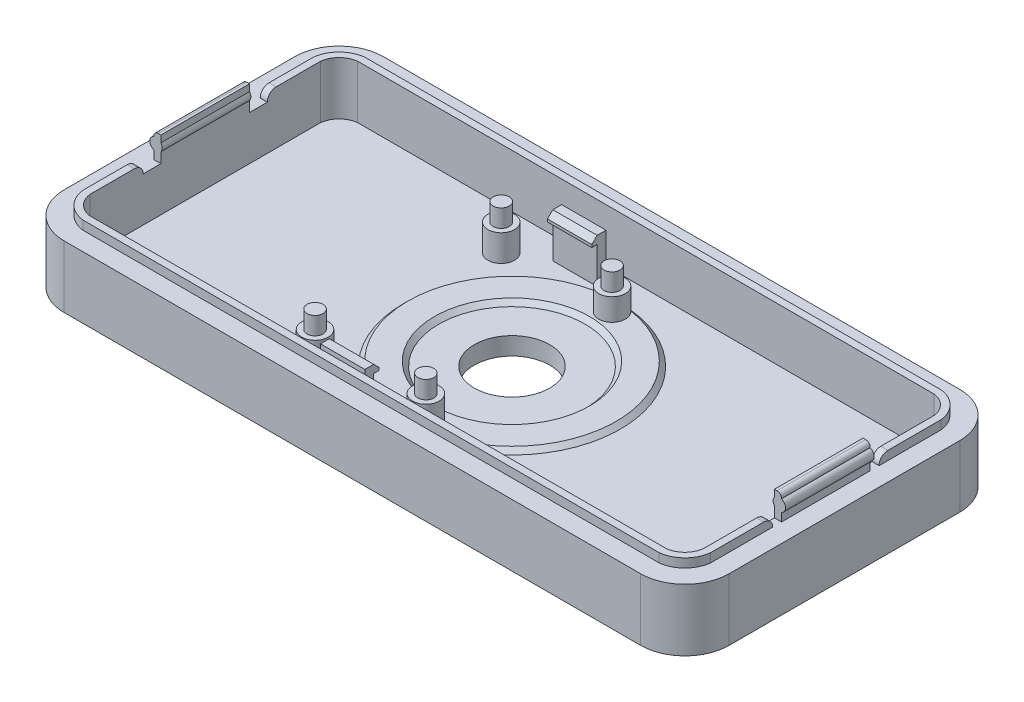
SolidWorks part; units mm, degrees
ref_plane "前视基准面" through (0, 0, 0) normal (0, 0, 1) x (1, 0, 0)
ref_plane "上视基准面" through (0, 0, 0) normal (0, 1, 0) x (1, 0, 0)
ref_plane "右视基准面" through (0, 0, 0) normal (1, 0, 0) x (0, 0, -1)
sketch "zero" plane through (0, 0, 0) normal (0, 1, 0) x (1, 0, 0)
  line L1 (-29.5, 15) -> (29.5, 15)
  line L2 (-32.5, 12) -> (-32.5, -12)
  line L3 (-29.5, -15) -> (29.5, -15)
  line L4 (32.5, 12) -> (32.5, -12)
  line L5 (-32.5, 15) -> (32.5, -15) construction
  line L6 (-32.5, -15) -> (32.5, 15) construction
  line L7 (-25.7, -15) -> (-14.5, -15)
  line L8 (-25.7, -15) -> (-25.7, -9.6569)
  line L9 (-25.7, -9.6569) -> (-14.5, -9.6569)
  line L10 (-14.5, -15) -> (-14.5, -9.6569)
  line L11 (5.2, -15) -> (12.7, -15)
  line L12 (5.2, -15) -> (5.2, -11)
  line L13 (5.2, -11) -> (12.7, -11)
  line L14 (12.7, -15) -> (12.7, -11)
  line L15 (17.8, -15) -> (25.3, -15)
  line L16 (17.8, -15) -> (17.8, -11)
  line L17 (17.8, -11) -> (25.3, -11)
  line L18 (25.3, -15) -> (25.3, -11)
  line L19 (-32.5, 7.7) -> (-19.5, 7.7)
  line L20 (-32.5, 7.7) -> (-32.5, -4.3)
  line L21 (-32.5, -4.3) -> (-19.5, -4.3)
  line L22 (-19.5, 7.7) -> (-19.5, -4.3)
  line L23 (-25.5, 14) -> (25.5, 14)
  line L24 (-25.5, 14) -> (-25.5, 8.8)
  line L25 (-25.5, 8.8) -> (25.5, 8.8)
  line L26 (25.5, 14) -> (25.5, 8.8)
  line L27 (-19.5, 7.2329) -> (-35.5, 7.2329)
  line L28 (-19.5, 7.2329) -> (-19.5, -3.7671)
  line L29 (-19.5, -3.7671) -> (-35.5, -3.7671)
  line L30 (-35.5, 7.2329) -> (-35.5, -3.7671)
  arc A0 (29.5, -15) -> (32.5, -12) centre (29.5, -12) ccw
  arc A1 (29.5, 15) -> (32.5, 12) centre (29.5, 12) cw
  arc A2 (-32.5, -12) -> (-29.5, -15) centre (-29.5, -12) ccw
  arc A3 (-29.5, 15) -> (-32.5, 12) centre (-29.5, 12) ccw
  circle A4 centre (-29, 11.4) radius 3
  circle A5 centre (-29, -11.5) radius 3
  circle A6 centre (29, 11.4) radius 3
  circle A7 centre (29, -11.5) radius 3
  circle A8 centre (-29, 11.4) radius 1.375
  circle A9 centre (-29, -11.5) radius 1.375
  circle A10 centre (29, -11.5) radius 1.375
  circle A11 centre (29, 11.4) radius 1.375
  point P0 (0, 0)
  dimension "D3" = 3
  dimension "D4" = 6
  dimension "D9" = 2.75
  dimension "D1" = 65
  dimension "D2" = 30
  dimension "D5" = 3.6
  dimension "D6" = 3.5
  dimension "D7" = 3.5
  dimension "D8" = 3.5
  dimension "D10" = 12
  dimension "D11" = 7.3
  dimension "D12" = 13
  dimension "D13" = 11.2
  dimension "D14" = 6.8
  dimension "D15" = 19.7
  dimension "D16" = 7.5
  dimension "D17" = 7.5
  dimension "D18" = 5.1
  dimension "D19" = 4
  dimension "D20" = 5.2
  dimension "D21" = 7
  dimension "D22" = 7
  dimension "D23" = 1
  dimension "D24" = 11
  dimension "D25" = 16
sketch "sugar" plane through (0, 0, 0) normal (0, 1, 0) x (1, 0, 0)
  line L1 (-29.5, 15) -> (29.5, 15)
  line L2 (-32.5, 12) -> (-32.5, -12)
  line L3 (-29.5, -15) -> (29.5, -15)
  line L4 (32.5, 12) -> (32.5, -12)
  line L5 (-32.5, 15) -> (32.5, -15) construction
  line L6 (-32.5, -15) -> (32.5, 15) construction
  line L7 (23.5, -11.5) -> (19.5, -11.5)
  line L8 (23.5, -11.5) -> (23.5, -13.9082)
  line L9 (23.5, -13.9082) -> (19.5, -13.9082)
  line L10 (19.5, -11.5) -> (19.5, -13.9082)
  line L11 (16, -11.0071) -> (8.5, -11.0071)
  line L12 (16, -11.0071) -> (16, -15)
  line L13 (16, -15) -> (8.5, -15)
  line L14 (8.5, -11.0071) -> (8.5, -15)
  line L15 (20.5, -13.9082) -> (22.5, -13.9082)
  line L16 (20.5, -13.9082) -> (20.5, -14.8173)
  line L17 (20.5, -14.8173) -> (22.5, -14.8173)
  line L18 (22.5, -13.9082) -> (22.5, -14.8173)
  arc A0 (29.5, 15) -> (32.5, 12) centre (29.5, 12) cw
  arc A1 (29.5, -15) -> (32.5, -12) centre (29.5, -12) ccw
  arc A2 (-32.5, -12) -> (-29.5, -15) centre (-29.5, -12) ccw
  arc A3 (-29.5, 15) -> (-32.5, 12) centre (-29.5, 12) ccw
  circle A4 centre (-29, 11.4) radius 3
  circle A5 centre (-29, 11.4) radius 1.375
  circle A6 centre (-29, -11.5) radius 3
  circle A7 centre (-29, -11.5) radius 1.375
  circle A8 centre (29, 11.4) radius 3
  circle A9 centre (29, 11.4) radius 1.375
  circle A10 centre (29, -11.5) radius 3
  circle A11 centre (29, -11.5) radius 1.375
  dimension "D3" = 3
  dimension "D1" = 65
  dimension "D2" = 30
  dimension "D4" = 9
  dimension "D5" = 4
  dimension "D6" = 3.5
  dimension "D7" = 7.5
  dimension "D8" = 2
  dimension "D9" = 1
sketch "case" plane through (0, 0, 0) normal (0, 1, 0) x (1, 0, 0)
  line L1 (-34.0422, 18) -> (30.9578, 18)
  line L2 (-39.0422, 13) -> (-39.0422, -13)
  line L3 (-34.0422, -18) -> (30.9578, -18)
  line L4 (35.9578, 13) -> (35.9578, -13)
  line L5 (-39.0422, 18) -> (35.9578, -18) construction
  line L6 (-39.0422, -18) -> (35.9578, 18) construction
  arc A0 (-39.0422, -13) -> (-34.0422, -18) centre (-34.0422, -13) ccw
  arc A1 (30.9578, -18) -> (35.9578, -13) centre (30.9578, -13) ccw
  arc A2 (30.9578, 18) -> (35.9578, 13) centre (30.9578, 13) cw
  arc A3 (-34.0422, 18) -> (-39.0422, 13) centre (-34.0422, 13) ccw
  point P0 (-1.5422, 0)
  point P3 (-1.5422, 0)
  dimension "D3" = 5
  dimension "D1" = 75
  dimension "D2" = 36
extrude "凸台-拉伸2" add sketch "case" along normal blind 7
sketch "草图2" plane through (0, 0, 0) normal (0, 1, 0) x (1, 0, 0)
  line L4 (-34.0422, -15.1) -> (30.9578, -15.1)
  line L5 (33.0578, -13) -> (33.0578, 13)
  line L6 (30.9578, 15.1) -> (-34.0422, 15.1)
  line L7 (-36.1422, 13) -> (-36.1422, -13)
  line L12 (33.8578, -13) -> (33.8578, 13)
  line L13 (30.9578, 15.9) -> (-34.0422, 15.9)
  line L14 (-36.9422, 13) -> (-36.9422, -13)
  line L15 (-34.0422, -15.9) -> (30.9578, -15.9)
  arc A4 (30.9578, -15.1) -> (33.0578, -13) centre (30.6746, -12.7168) ccw
  arc A5 (33.0578, 13) -> (30.9578, 15.1) centre (30.6746, 12.7168) ccw
  arc A6 (-34.0422, 15.1) -> (-36.1422, 13) centre (-33.759, 12.7168) ccw
  arc A7 (-36.1422, -13) -> (-34.0422, -15.1) centre (-33.759, -12.7168) ccw
  arc A12 (30.9578, -15.9) -> (33.8578, -13) centre (30.5796, -12.6217) ccw
  arc A13 (33.8578, 13) -> (30.9578, 15.9) centre (30.5796, 12.6217) ccw
  arc A14 (-34.0422, 15.9) -> (-36.9422, 13) centre (-33.6639, 12.6217) ccw
  arc A15 (-36.9422, -13) -> (-34.0422, -15.9) centre (-33.6639, -12.6217) ccw
ref_plane "基准面1" through (0, 7, 0) normal (0, 1, 0) x (1, 0, 0)
sketch "草图3" plane through (0, 7, 0) normal (0, 1, 0) x (1, 0, 0)
  line L4 (-34.0422, -15.1) -> (30.9578, -15.1)
  line L5 (33.0578, -13) -> (33.0578, 13)
  line L6 (30.9578, 15.1) -> (-34.0422, 15.1)
  line L7 (-36.1422, 13) -> (-36.1422, -13)
  line L8 (-34.0422, -15.1) -> (30.9578, -15.1)
  line L9 (33.0578, -13) -> (33.0578, 13)
  line L10 (30.9578, 15.1) -> (-34.0422, 15.1)
  line L11 (-36.1422, 13) -> (-36.1422, -13)
  line L12 (-36.9422, 13) -> (-36.9422, -13)
  line L13 (-34.0422, -15.9) -> (30.9578, -15.9)
  line L14 (33.8578, -13) -> (33.8578, 13)
  line L15 (30.9578, 15.9) -> (-34.0422, 15.9)
  line L16 (-36.9422, 13) -> (-36.9422, -13)
  line L17 (-34.0422, -15.9) -> (30.9578, -15.9)
  line L18 (33.8578, -13) -> (33.8578, 13)
  line L19 (30.9578, 15.9) -> (-34.0422, 15.9)
  arc A4 (30.9578, -15.1) -> (33.0578, -13) centre (30.6746, -12.7168) ccw
  arc A5 (33.0578, 13) -> (30.9578, 15.1) centre (30.6746, 12.7168) ccw
  arc A6 (-34.0422, 15.1) -> (-36.1422, 13) centre (-33.759, 12.7168) ccw
  arc A7 (-36.1422, -13) -> (-34.0422, -15.1) centre (-33.759, -12.7168) ccw
  arc A8 (30.9578, -15.1) -> (33.0578, -13) centre (30.6746, -12.7168) ccw
  arc A9 (33.0578, 13) -> (30.9578, 15.1) centre (30.6746, 12.7168) ccw
  arc A10 (-34.0422, 15.1) -> (-36.1422, 13) centre (-33.759, 12.7168) ccw
  arc A11 (-36.1422, -13) -> (-34.0422, -15.1) centre (-33.759, -12.7168) ccw
  arc A12 (-36.9422, -13) -> (-34.0422, -15.9) centre (-33.6639, -12.6217) ccw
  arc A13 (30.9578, -15.9) -> (33.8578, -13) centre (30.5796, -12.6217) ccw
  arc A14 (33.8578, 13) -> (30.9578, 15.9) centre (30.5796, 12.6217) ccw
  arc A15 (-34.0422, 15.9) -> (-36.9422, 13) centre (-33.6639, 12.6217) ccw
  arc A16 (-36.9422, -13) -> (-34.0422, -15.9) centre (-33.6639, -12.6217) ccw
  arc A17 (30.9578, -15.9) -> (33.8578, -13) centre (30.5796, -12.6217) ccw
  arc A18 (33.8578, 13) -> (30.9578, 15.9) centre (30.5796, 12.6217) ccw
  arc A19 (-34.0422, 15.9) -> (-36.9422, 13) centre (-33.6639, 12.6217) ccw
  dimension "D1" = 0
  dimension "D2" = 0
extrude "凸台-拉伸4" add sketch "草图3" along normal blind 1
ref_plane "基准面3" through (33.8578, 0, 0) normal (1, 0, 0) x (0, 0, -1)
sketch "草图7" plane through (0, 7, 0) normal (0, 1, 0) x (1, 0, 0)
  line L0 (-36.9422, 13) -> (-36.9422, -13) construction
  line L1 (-36.9422, 5) -> (-36.1422, 5)
  line L2 (-36.9422, 5) -> (-36.9422, -5)
  line L3 (-36.9422, -5) -> (-36.1422, -5)
  line L4 (-36.1422, 5) -> (-36.1422, -5)
  line L5 (-36.1422, 13) -> (-36.1422, -13) construction
  point P10 (-36.1422, 0)
  dimension "D1" = 5
  dimension "D2" = 10
extrude "凸台-拉伸8" add sketch "草图7" along normal blind 2.8
ref_plane "基准面5" through (0, 0, 5) normal (0, 0, 1) x (1, 0, 0)
sketch "草图8" plane through (0, 0, 5) normal (0, 0, 1) x (1, 0, 0)
  line L0 (-34.0422, 7) -> (-39.0422, 7) construction
  line L1 (-36.9422, 9.8) -> (-36.9422, 8) construction
  circle A0 centre (-36.6922, 8.6) radius 0.7
  dimension "D1" = 1.4
  dimension "D2" = 1.6
  dimension "D3" = 0.25
extrude "凸台-拉伸9" add sketch "草图8" against normal blind 10
fillet "圆角3" radius 0.5 1 edges at (-36.9422, 9.8, 0)
sketch "草图13" plane through (0, 8, 0) normal (0, 1, 0) x (1, 0, 0)
  line L0 (-36.9422, -5) -> (-36.9422, -13) construction
  line L1 (-36.1422, -5) -> (-36.9422, -5)
  line L2 (-36.1422, -5) -> (-36.1422, -7)
  line L3 (-36.1422, -7) -> (-36.9422, -7)
  line L4 (-36.9422, -5) -> (-36.9422, -7)
  line L5 (-36.9422, 13) -> (-36.9422, 5) construction
  line L6 (-36.1422, 5) -> (-36.9422, 5)
  line L7 (-36.1422, 5) -> (-36.1422, 7)
  line L8 (-36.1422, 7) -> (-36.9422, 7)
  line L9 (-36.9422, 5) -> (-36.9422, 7)
  dimension "D1" = 2
  dimension "D2" = 2
extrude "切除-拉伸2" cut sketch "草图13" against normal blind 1
sketch "草图15" plane through (0, 7, 0) normal (0, 1, 0) x (1, 0, 0)
  line L4 (-34.0422, -15.1) -> (30.9578, -15.1)
  line L5 (33.0578, -13) -> (33.0578, 13)
  line L6 (30.9578, 15.1) -> (-34.0422, 15.1)
  line L7 (-36.1422, 13) -> (-36.1422, -13)
  line L8 (-34.0422, -15.1) -> (30.9578, -15.1)
  line L9 (33.0578, -13) -> (33.0578, 13)
  line L10 (30.9578, 15.1) -> (-34.0422, 15.1)
  line L11 (-36.1422, 13) -> (-36.1422, -13)
  arc A4 (30.9578, -15.1) -> (33.0578, -13) centre (30.6746, -12.7168) ccw
  arc A5 (33.0578, 13) -> (30.9578, 15.1) centre (30.6746, 12.7168) ccw
  arc A6 (-34.0422, 15.1) -> (-36.1422, 13) centre (-33.759, 12.7168) ccw
  arc A7 (-36.1422, -13) -> (-34.0422, -15.1) centre (-33.759, -12.7168) ccw
  arc A8 (30.9578, -15.1) -> (33.0578, -13) centre (30.6746, -12.7168) ccw
  arc A9 (33.0578, 13) -> (30.9578, 15.1) centre (30.6746, 12.7168) ccw
  arc A10 (-34.0422, 15.1) -> (-36.1422, 13) centre (-33.759, 12.7168) ccw
  arc A11 (-36.1422, -13) -> (-34.0422, -15.1) centre (-33.759, -12.7168) ccw
  dimension "D1" = 0
extrude "切除-拉伸3" cut sketch "草图15" against normal blind 5
sketch "草图19" plane through (0, 2, 0) normal (0, 1, 0) x (1, 0, 0)
  line L0 (30.9578, 18) -> (-34.0422, 18) construction
  circle A0 centre (-1.5422, 0) radius 4.25
  point P2 (0, 0)
  point P5 (-1.5422, 18)
  dimension "D1" = 8.5
extrude "切除-拉伸4" cut sketch "草图19" against normal blind 3
sketch "草图21" plane through (0, 2, 0) normal (0, 1, 0) x (1, 0, 0)
  line L0 (-34.0422, -15.1) -> (30.9578, -15.1) construction
  line L1 (30.9578, 15.1) -> (-34.0422, 15.1) construction
  line L5 (30.9578, 15.1) -> (-34.0422, 15.1) construction
  line L6 (-34.0422, -15.1) -> (30.9578, -15.1) construction
  circle A0 centre (-13.2575, 10.5) radius 1.5
  circle A1 centre (-0.7575, 10.5) radius 1.5
  circle A2 centre (-13.2575, -10.5) radius 1.5
  circle A3 centre (-0.7575, -10.5) radius 1.5
  circle A4 centre (-1.5422, 0) radius 4.25 construction
  point P2 (0, 0)
  point P8 (0, 0)
  point P11 (0, 0)
  dimension "D1" = 3
  dimension "D2" = 12.5
  dimension "D3" = 12.5
  dimension "D4" = 4.6
  dimension "D5" = 4.6
  dimension "D7" = 11.7153
  dimension "D8" = 4.6
  dimension "D9" = 4.6
extrude "凸台-拉伸11" add sketch "草图21" along normal blind 3
sketch "草图22" plane through (0, 5, 0) normal (0, 1, 0) x (1, 0, 0)
  circle A0 centre (-13.2575, -10.5) radius 0.9
  circle A1 centre (-0.7575, -10.5) radius 0.9
  circle A2 centre (-13.2575, 10.5) radius 0.9
  circle A3 centre (-0.7575, 10.5) radius 0.9
  circle A4 centre (-13.2575, 10.5) radius 1.5 construction
  circle A5 centre (-13.2575, -10.5) radius 1.5 construction
  circle A6 centre (-0.7575, -10.5) radius 1.5 construction
  circle A7 centre (-0.7575, 10.5) radius 1.5 construction
  dimension "D1" = 1.8
extrude "凸台-拉伸12" add sketch "草图22" along normal blind 2
sketch "草图28" plane through (0, 2, 0) normal (0, 1, 0) x (1, 0, 0)
  line L0 (30.9578, 15.1) -> (-34.0422, 15.1) construction
  line L1 (-4.5422, -12.6) -> (-9.5422, -12.6)
  line L2 (-4.5422, -12.6) -> (-4.5422, -13.6)
  line L3 (-4.5422, -13.6) -> (-9.5422, -13.6)
  line L4 (-9.5422, -12.6) -> (-9.5422, -13.6)
  line L5 (-4.5422, 13.6) -> (-9.5422, 13.6)
  line L6 (-4.5422, 13.6) -> (-4.5422, 12.6)
  line L7 (-4.5422, 12.6) -> (-9.5422, 12.6)
  line L8 (-9.5422, 13.6) -> (-9.5422, 12.6)
  line L9 (-34.0422, -15.1) -> (30.9578, -15.1) construction
  circle A0 centre (-1.5422, 0) radius 4.25 construction
  dimension "D1" = 1
  dimension "D2" = 1.5
  dimension "D3" = 5
  dimension "D4" = 1.5
  dimension "D5" = 3
extrude "凸台-拉伸16" add sketch "草图28" along normal blind 5
fillet "圆角4" radius 1 2 edges at (-7.0422, 2, -13.6) (-7.0422, 2, 13.6)
sketch "草图29" plane through (0, 0, 12.6) normal (0, 0, -1) x (-1, 0, 0)
  line L0 (9.5422, 7) -> (9.5422, 2) construction
  line L1 (4.5422, 7) -> (9.5422, 7)
  line L2 (4.5422, 7) -> (4.5422, 6.1)
  line L3 (4.5422, 6.1) -> (9.5422, 6.1)
  line L4 (9.5422, 7) -> (9.5422, 6.1)
  dimension "D1" = 0.9
extrude "凸台-拉伸17" add sketch "草图29" along normal blind 0.6
sketch "草图30" plane through (0, 0, -12.6) normal (0, 0, 1) x (1, 0, 0)
  line L0 (-4.5422, 7) -> (-4.5422, 2) construction
  line L1 (-9.5422, 7) -> (-4.5422, 7)
  line L2 (-9.5422, 7) -> (-9.5422, 6.1)
  line L3 (-9.5422, 6.1) -> (-4.5422, 6.1)
  line L4 (-4.5422, 7) -> (-4.5422, 6.1)
  dimension "D1" = 0.9
extrude "凸台-拉伸18" add sketch "草图30" along normal blind 0.6
chamfer "倒角5" distance 0.6 angle 45 2 edges at (-7.0422, 7, -12) (-7.0422, 7, 12)
sketch "草图32" plane through (0, 0, 0) normal (0, 1, 0) x (1, 0, 0)
  line L75 (-14.6761, -9.5363) -> (-15.4836, -9.6938)
  line L76 (-12.4748, -8.5613) -> (-14.1869, -8.5613)
  line L77 (-12.4748, -7.6298) -> (-12.4748, -8.5613)
  line L78 (-15.4702, -7.6298) -> (-12.4748, -7.6298)
  line L79 (-15.4702, -8.3938) -> (-15.4702, -7.6298)
  line L80 (-14.9509, -8.4574) -> (-15.4702, -8.3938)
  line L81 (-14.9509, -8.4776) -> (-14.9509, -8.4574)
  line L82 (-13.8452, -6.0752) -> (-13.366, -6.0752)
  line L83 (-12.4748, -7.0133) -> (-14.1769, -7.0133)
  line L84 (-12.4748, -6.2494) -> (-12.4748, -7.0133)
  line L85 (-12.7763, -6.1824) -> (-12.4748, -6.2494)
  line L86 (-12.7763, -6.1589) -> (-12.7763, -6.1824)
  line L87 (-15.1519, -4.5104) -> (-14.5354, -4.8388)
  line L88 (-12.3475, -2.6743) -> (-12.3475, -2.9592)
  line L89 (-12.5853, -1.763) -> (-12.5586, -1.763)
  line L90 (-13.681, -1.8199) -> (-13.6609, -1.8199)
  line L91 (-15.4702, -4.2424) -> (-15.4702, -3.1434)
  line L92 (-14.7934, -4.2424) -> (-15.4702, -4.2424)
  line L93 (-14.7934, -3.78) -> (-14.7934, -4.2424)
  line L94 (-13.0645, -3.1367) -> (-13.0645, -2.6643)
  line L95 (-15.4702, -0.8717) -> (-15.4702, 0.0664)
  line L96 (-12.4748, -0.8717) -> (-15.4702, -0.8717)
  line L97 (-12.4748, -0.1078) -> (-12.4748, -0.8717)
  line L98 (-12.8869, -0.0408) -> (-12.4748, -0.1078)
  line L99 (-12.8869, -0.0207) -> (-12.8869, -0.0408)
  line L100 (-15.4702, 1.849) -> (-13.6173, 1.849)
  line L101 (-15.4702, 0.9141) -> (-15.4702, 1.849)
  line L102 (-13.7346, 0.9141) -> (-15.4702, 0.9141)
  line L103 (-15.4702, 0.0664) -> (-13.5068, 0.0664)
  line L104 (-13.614, 4.7204) -> (-12.964, 5.2531)
  line L105 (-14.207, 4.3083) -> (-13.9959, 3.809)
  line L106 (-15.3596, 2.8776) -> (-15.9493, 2.4085)
  line L107 (-14.7029, 3.0686) -> (-14.8973, 3.5577)
  line L108 (-15.3362, 5.8361) -> (-15.3362, 6.3153)
  line L109 (-12.4748, 5.8361) -> (-15.3362, 5.8361)
  line L110 (-12.4748, 6.3153) -> (-12.4748, 5.8361)
  line L111 (-15.3362, 6.3153) -> (-12.4748, 6.3153)
  line L112 (-15.9393, 9.0091) -> (-15.9393, 8.4529)
  line L113 (-14.4014, 9.0091) -> (-15.9393, 9.0091)
  line L114 (-14.4014, 8.4328) -> (-14.4014, 9.0091)
  line L115 (-14.006, 9.0091) -> (-14.006, 8.3692)
  line L116 (-12.4748, 9.0091) -> (-14.006, 9.0091)
  line L117 (-12.4748, 9.4984) -> (-12.4748, 9.0091)
  line L118 (-16.3346, 9.4984) -> (-12.4748, 9.4984)
  line L119 (-16.3346, 8.396) -> (-16.3346, 9.4984)
  spline S0 degree 3 poles (-15.4836, -9.6938) (-15.5205, -9.61) (-15.5439, -9.5095) (-15.5439, -9.3319) knots 10 10 10 10 11 11 11 11
  spline S1 degree 3 poles (-14.723, -9.208) (-14.723, -9.342) (-14.7029, -9.4291) (-14.6761, -9.5363) knots 8 8 8 8 9 9 9 9
  spline S2 degree 3 poles (-14.1869, -8.5613) (-14.5823, -8.7188) (-14.723, -8.9869) (-14.723, -9.208) knots 7 7 7 7 8 8 8 8
  spline S3 degree 3 poles (-15.5439, -9.3319) (-15.5439, -9.0304) (-15.3496, -8.6987) (-14.9509, -8.4776) knots 0 0 0 0 1 1 1 1
  spline S4 degree 3 poles (-13.3861, -5.3012) (-13.5972, -5.3012) (-13.7648, -5.4922) (-13.8452, -6.0752) knots 2 2 2 2 3 3 3 3
  spline S5 degree 3 poles (-13.1282, -5.6229) (-13.1282, -5.4285) (-13.2119, -5.3012) (-13.3861, -5.3012) knots 1 1 1 1 2 2 2 2
  spline S6 degree 3 poles (-13.366, -6.0752) (-13.2186, -5.9378) (-13.1282, -5.8138) (-13.1282, -5.6229) knots 0 0 0 0 1 1 1 1
  spline S7 degree 3 poles (-14.1769, -7.0133) (-15.1151, -7.0133) (-15.5439, -6.5744) (-15.5439, -5.8004) knots 11 11 11 11 12 12 12 12
  spline S8 degree 3 poles (-12.4011, -5.3012) (-12.4011, -5.6329) (-12.5552, -5.911) (-12.7763, -6.1589) knots 6 6 6 6 7 7 7 7
  spline S9 degree 3 poles (-13.3124, -4.4099) (-12.8132, -4.4099) (-12.4011, -4.7483) (-12.4011, -5.3012) knots 5 5 5 5 6 6 6 6
  spline S10 degree 3 poles (-14.4148, -6.0752) (-14.2874, -4.9058) (-13.9457, -4.4099) (-13.3124, -4.4099) knots 4 4 4 4 5 5 5 5
  spline S11 degree 3 poles (-14.7967, -5.6229) (-14.7967, -5.9277) (-14.656, -6.0551) (-14.4148, -6.0752) knots 3 3 3 3 4 4 4 4
  spline S12 degree 3 poles (-14.5354, -4.8388) (-14.7029, -5.137) (-14.7967, -5.385) (-14.7967, -5.6229) knots 2 2 2 2 3 3 3 3
  spline S13 degree 3 poles (-15.5439, -5.8004) (-15.5439, -5.3347) (-15.3864, -4.9058) (-15.1519, -4.5104) knots 0 0 0 0 1 1 1 1
  spline S14 degree 3 poles (-12.133, -3.3947) (-11.942, -3.3947) (-11.8013, -3.1267) (-11.8013, -2.7413) knots 5 5 5 5 6 6 6 6
  spline S15 degree 3 poles (-12.3475, -2.9592) (-12.3475, -3.2372) (-12.3106, -3.3947) (-12.133, -3.3947) knots 4 4 4 4 5 5 5 5
  spline S16 degree 3 poles (-12.3843, -2.2454) (-12.3575, -2.3426) (-12.3475, -2.4566) (-12.3475, -2.6743) knots 2 2 2 2 3 3 3 3
  spline S17 degree 3 poles (-12.1163, -2.1047) (-12.2168, -2.1047) (-12.3006, -2.1516) (-12.3843, -2.2454) knots 1 1 1 1 2 2 2 2
  spline S18 degree 3 poles (-11.8013, -2.7413) (-11.8013, -2.356) (-11.9052, -2.1047) (-12.1163, -2.1047) knots 0 0 0 0 1 1 1 1
  spline S19 degree 3 poles (-14.9174, -2.6676) (-14.9174, -2.8888) (-14.7599, -3.0462) (-14.455, -3.0462) (-14.1434, -3.0462) (-13.9859, -2.8888) (-13.9859, -2.6676) knots 0 0 0 0 1 1 1 2 2 2 2
  spline S20 degree 3 poles (-13.9859, -2.6676) (-13.9859, -2.4532) (-14.1434, -2.289) (-14.455, -2.289) (-14.7599, -2.289) (-14.9174, -2.4532) (-14.9174, -2.6676) knots 2 2 2 2 3 3 3 4 4 4 4
  spline S21 degree 3 poles (-12.2972, -4.2893) (-12.84, -4.2893) (-13.0645, -3.8739) (-13.0645, -3.1367) knots 19 19 19 19 20 20 20 20
  spline S22 degree 3 poles (-11.215, -2.5939) (-11.215, -3.6359) (-11.6639, -4.2893) (-12.2972, -4.2893) knots 18 18 18 18 19 19 19 19
  spline S23 degree 3 poles (-11.9688, -1.3374) (-11.4328, -1.3374) (-11.215, -1.9037) (-11.215, -2.5939) knots 17 17 17 17 18 18 18 18
  spline S24 degree 3 poles (-12.5586, -1.763) (-12.4178, -1.4849) (-12.2168, -1.3374) (-11.9688, -1.3374) knots 16 16 16 16 17 17 17 17
  spline S25 degree 3 poles (-13.1013, -1.4882) (-12.8501, -1.4882) (-12.6926, -1.6055) (-12.5853, -1.763) knots 14 14 14 14 15 15 15 15
  spline S26 degree 3 poles (-13.6609, -1.8199) (-13.5235, -1.6256) (-13.3124, -1.4882) (-13.1013, -1.4882) knots 13 13 13 13 14 14 14 14
  spline S27 degree 3 poles (-14.455, -1.4145) (-14.1065, -1.4145) (-13.8284, -1.6089) (-13.681, -1.8199) knots 11 11 11 11 12 12 12 12
  spline S28 degree 3 poles (-15.5439, -2.6676) (-15.5439, -2.021) (-15.1888, -1.4145) (-14.455, -1.4145) knots 10 10 10 10 11 11 11 11
  spline S86 degree 3 poles (-15.4702, -3.1434) (-15.5205, -3.006) (-15.5439, -2.8419) (-15.5439, -2.6676) knots 9 9 9 9 10 10 10 10
  spline S87 degree 3 poles (-14.4282, -3.8638) (-14.5723, -3.8638) (-14.7096, -3.8269) (-14.7934, -3.78) knots 5 5 5 5 6 6 6 6
  spline S88 degree 3 poles (-13.423, -2.6676) (-13.423, -3.331) (-13.7279, -3.8638) (-14.4282, -3.8638) knots 4 4 4 4 5 5 5 5
  spline S89 degree 3 poles (-13.4766, -2.3158) (-13.4398, -2.4465) (-13.423, -2.5671) (-13.423, -2.6676) knots 3 3 3 3 4 4 4 4
  spline S90 degree 3 poles (-13.2655, -2.222) (-13.366, -2.222) (-13.4129, -2.2454) (-13.4766, -2.3158) knots 2 2 2 2 3 3 3 3
  spline S91 degree 3 poles (-13.0645, -2.6643) (-13.0645, -2.3426) (-13.1282, -2.222) (-13.2655, -2.222) knots 1 1 1 1 2 2 2 2
  spline S92 degree 3 poles (-12.4011, 0.9175) (-12.4011, 0.5087) (-12.5921, 0.2272) (-12.8869, -0.0207) knots 7 7 7 7 8 8 8 8
  spline S93 degree 3 poles (-13.6173, 1.849) (-12.8702, 1.849) (-12.4011, 1.5708) (-12.4011, 0.9175) knots 6 6 6 6 7 7 7 7
  spline S94 degree 3 poles (-13.2019, 0.5657) (-13.2019, 0.8036) (-13.3191, 0.9141) (-13.7346, 0.9141) knots 2 2 2 2 3 3 3 3
  spline S95 degree 3 poles (-13.5068, 0.0664) (-13.2856, 0.2239) (-13.2019, 0.3546) (-13.2019, 0.5657) knots 1 1 1 1 2 2 2 2
  spline S96 degree 3 poles (-13.6274, 2.2913) (-14.1802, 2.2913) (-14.5086, 2.5827) (-14.7029, 3.0686) knots 15 15 15 15 16 16 16 16
  spline S97 degree 3 poles (-12.4011, 3.789) (-12.4011, 2.8407) (-12.974, 2.2913) (-13.6274, 2.2913) knots 14 14 14 14 15 15 15 15
  spline S98 degree 3 poles (-12.964, 5.2531) (-12.5921, 4.8477) (-12.4011, 4.2983) (-12.4011, 3.789) knots 13 13 13 13 14 14 14 14
  spline S99 degree 3 poles (-13.2119, 3.7688) (-13.2119, 4.0771) (-13.3761, 4.4423) (-13.614, 4.7204) knots 11 11 11 11 12 12 12 12
  spline S100 degree 3 poles (-13.5537, 3.2562) (-13.3426, 3.2562) (-13.2119, 3.4204) (-13.2119, 3.7688) knots 10 10 10 10 11 11 11 11
  spline S101 degree 3 poles (-13.9959, 3.809) (-13.8552, 3.474) (-13.7815, 3.2562) (-13.5537, 3.2562) knots 9 9 9 9 10 10 10 10
  spline S102 degree 3 poles (-15.2826, 5.1057) (-14.713, 5.1057) (-14.3712, 4.7204) (-14.207, 4.3083) knots 7 7 7 7 8 8 8 8
  spline S103 degree 3 poles (-16.4687, 3.6817) (-16.4687, 4.516) (-15.9393, 5.1057) (-15.2826, 5.1057) knots 6 6 6 6 7 7 7 7
  spline S104 degree 3 poles (-15.9493, 2.4085) (-16.2944, 2.7502) (-16.4687, 3.2294) (-16.4687, 3.6817) knots 5 5 5 5 6 6 6 6
  spline S105 degree 3 poles (-15.6612, 3.6817) (-15.6612, 3.3768) (-15.5573, 3.1356) (-15.3596, 2.8776) knots 3 3 3 3 4 4 4 4
  spline S106 degree 3 poles (-15.3362, 4.1508) (-15.5439, 4.1508) (-15.6612, 3.9732) (-15.6612, 3.6817) knots 2 2 2 2 3 3 3 3
  spline S107 degree 3 poles (-14.8973, 3.5577) (-15.0346, 3.9029) (-15.1184, 4.1508) (-15.3362, 4.1508) knots 1 1 1 1 2 2 2 2
  spline S108 degree 3 poles (-16.5457, 6.074) (-16.5457, 6.265) (-16.4318, 6.4057) (-16.2341, 6.4057) (-16.0566, 6.4057) (-15.9259, 6.265) (-15.9259, 6.074) knots 0 0 0 0 1 1 1 2 2 2 2
  spline S109 degree 3 poles (-15.9259, 6.074) (-15.9259, 5.8831) (-16.0566, 5.7423) (-16.2341, 5.7423) (-16.4318, 5.7423) (-16.5457, 5.8831) (-16.5457, 6.074) knots 2 2 2 2 3 3 3 4 4 4 4
  spline S110 degree 3 poles (-15.2022, 7.4343) (-14.6493, 7.4343) (-14.4014, 7.7527) (-14.4014, 8.4328) knots 4 4 4 4 5 5 5 5
  spline S111 degree 3 poles (-15.9393, 8.4529) (-15.9393, 7.7761) (-15.7617, 7.4343) (-15.2022, 7.4343) knots 3 3 3 3 4 4 4 4
  spline S112 degree 3 poles (-15.2022, 6.9485) (-16.0465, 6.9485) (-16.3346, 7.5282) (-16.3346, 8.396) knots 6 6 6 6 7 7 7 7
  spline S113 degree 3 poles (-14.006, 8.3692) (-14.006, 7.5282) (-14.388, 6.9485) (-15.2022, 6.9485) knots 5 5 5 5 6 6 6 6
sketch "草图33" plane through (0, 0, 0) normal (0, -1, 0) x (1, 0, 0)
  line L0 (31.4528, 12.8823) -> (31.1283, 13.0694)
  line L1 (31.1283, 13.0694) -> (29.4447, 14.0408)
  line L2 (29.4447, 14.0408) -> (29.1201, 14.2301)
  line L3 (28.4395, 14.2301) -> (28.1149, 14.0408)
  line L4 (28.1149, 14.0408) -> (26.4313, 13.0694)
  line L5 (26.4313, 13.0694) -> (26.1067, 12.8823)
  line L6 (25.7664, 12.2941) -> (25.7664, 9.5985)
  line L7 (26.1067, 9.0102) -> (26.4313, 8.8231)
  line L8 (26.4313, 8.8231) -> (28.1149, 7.8517)
  line L9 (28.1149, 7.8517) -> (28.4395, 7.6624)
  line L10 (29.1201, 7.6624) -> (29.4447, 7.8517)
  line L11 (29.4447, 7.8517) -> (31.1283, 8.8231)
  line L12 (31.1283, 8.8231) -> (31.4528, 9.0102)
  line L13 (31.7932, 9.5985) -> (31.7932, 12.2941)
  line L14 (26.5395, 12.6141) -> (28.622, 13.8177)
  line L15 (28.9398, 13.8177) -> (31.0111, 12.6118)
  line L16 (31.0134, 12.3346) -> (29.0007, 11.1311)
  line L17 (29.625, 9.0913) -> (29.3906, 8.9606)
  line L18 (29.368, 8.9223) -> (29.368, 8.2461)
  line L19 (29.3455, 8.2078) -> (28.9083, 7.9599)
  line L20 (28.8429, 7.9982) -> (28.8429, 10.0853)
  line L21 (28.8654, 10.1236) -> (29.6092, 10.5451)
  line L22 (31.1689, 9.2311) -> (30.7361, 8.9854)
  line L23 (30.6708, 9.0237) -> (30.6708, 10.0177)
  line L24 (30.6933, 10.056) -> (31.126, 10.2994)
  line L25 (31.1914, 10.2611) -> (31.1914, 9.2694)
  line L26 (29.5979, 9.4925) -> (29.3906, 9.3888)
  line L27 (29.368, 9.4362) -> (29.368, 9.9681)
  line L28 (29.3906, 10.0064) -> (29.5844, 10.1146)
  line L29 (29.3906, 9.3888) -> (29.3906, 8.9606)
  line L30 (29.368, 9.4362) -> (29.368, 8.9223)
  spline S0 degree 3 poles (29.1201, 14.2301) (29.0142, 14.2887) (28.897, 14.3203) (28.7798, 14.3203) knots 3 3 3 3 4 4 4 4
  spline S1 degree 3 poles (28.7798, 14.3203) (28.6626, 14.3203) (28.5454, 14.2887) (28.4395, 14.2301) knots 4 4 4 4 5 5 5 5
  spline S2 degree 3 poles (26.1067, 12.8823) (25.8971, 12.7606) (25.7664, 12.5352) (25.7664, 12.2941) knots 8 8 8 8 9 9 9 9
  spline S3 degree 3 poles (25.7664, 9.5985) (25.7664, 9.355) (25.8971, 9.1319) (26.1067, 9.0102) knots 10 10 10 10 11 11 11 11
  spline S4 degree 3 poles (28.4395, 7.6624) (28.5454, 7.6015) (28.6626, 7.5722) (28.7798, 7.5722) knots 14 14 14 14 15 15 15 15
  spline S5 degree 3 poles (28.7798, 7.5722) (28.897, 7.5722) (29.0142, 7.6015) (29.1201, 7.6624) knots 15 15 15 15 16 16 16 16
  spline S6 degree 3 poles (31.4528, 9.0102) (31.6647, 9.1319) (31.7932, 9.355) (31.7932, 9.5985) knots 19 19 19 19 20 20 20 20
  spline S7 degree 3 poles (31.7932, 12.2941) (31.7932, 12.5352) (31.6647, 12.7606) (31.4528, 12.8823) knots 21 21 21 21 22 22 22 22
  spline S8 degree 2 poles (28.5612, 11.1311) (26.5237, 12.3076) (26.5192, 12.3098) knots 0 0 0 1 1 1
  spline S9 degree 3 poles (26.5192, 12.3098) (26.4133, 12.3865) (26.4245, 12.5487) (26.5395, 12.6141) knots 1 1 1 1 2 2 2 2
  spline S10 degree 3 poles (28.622, 13.8177) (28.719, 13.874) (28.8407, 13.874) (28.9398, 13.8177) knots 3 3 3 3 4 4 4 4
  spline S11 degree 3 poles (31.0111, 12.6118) (31.117, 12.551) (31.1193, 12.3977) (31.0134, 12.3346) knots 5 5 5 5 6 6 6 6
  spline S12 degree 3 poles (29.0007, 11.1311) (28.8654, 11.0522) (28.6964, 11.0522) (28.5612, 11.1311) knots 7 7 7 7 8 8 8 8
  spline S13 degree 3 poles (29.368, 8.2461) (29.368, 8.2304) (29.3613, 8.2168) (29.3455, 8.2078) knots 3 3 3 3 4 4 4 4
  spline S14 degree 3 poles (28.9083, 7.9599) (28.879, 7.9441) (28.8429, 7.9644) (28.8429, 7.9982) knots 5 5 5 5 6 6 6 6
  spline S15 degree 3 poles (28.8429, 10.0853) (28.8429, 10.1011) (28.8497, 10.1168) (28.8654, 10.1236) knots 7 7 7 7 8 8 8 8
  spline S16 degree 3 poles (29.6092, 10.5451) (30.0915, 10.8178) (30.4904, 10.8719) (30.4904, 10.331) knots 9 9 9 9 10 10 10 10
  spline S17 degree 3 poles (30.4904, 10.331) (30.4904, 9.8103) (30.087, 9.3528) (29.625, 9.0913) knots 10 10 10 10 11 11 11 11
  spline S18 degree 3 poles (31.1914, 9.2694) (31.1914, 9.2536) (31.1824, 9.2378) (31.1689, 9.2311) knots 0 0 0 0 1 1 1 1
  spline S19 degree 3 poles (30.7361, 8.9854) (30.7068, 8.9696) (30.6708, 8.9899) (30.6708, 9.0237) knots 2 2 2 2 3 3 3 3
  spline S20 degree 3 poles (30.6708, 10.0177) (30.6708, 10.0334) (30.6798, 10.047) (30.6933, 10.056) knots 4 4 4 4 5 5 5 5
  spline S21 degree 3 poles (31.126, 10.2994) (31.1553, 10.3152) (31.1914, 10.2949) (31.1914, 10.2611) knots 6 6 6 6 7 7 7 7
  spline S22 degree 3 poles (30.9322, 10.9598) (31.1058, 11.059) (31.2297, 11.0161) (31.2297, 10.8584) (31.2297, 10.7028) (31.1058, 10.5203) (30.9322, 10.4234) knots 2 2 2 2 3 3 3 4 4 4 4
  spline S23 degree 3 poles (30.9322, 10.4234) (30.7564, 10.3219) (30.6325, 10.3648) (30.6325, 10.5203) (30.6325, 10.6803) (30.7564, 10.8606) (30.9322, 10.9598) knots 0 0 0 0 1 1 1 2 2 2 2
  spline S24 degree 3 poles (29.9766, 10.0402) (29.9766, 9.8261) (29.8549, 9.6368) (29.5979, 9.4925) knots 0 0 0 0 1 1 1 1
  spline S25 degree 3 poles (29.368, 9.9681) (29.368, 9.9839) (29.3771, 9.9996) (29.3906, 10.0064) knots 4 4 4 4 5 5 5 5
  spline S26 degree 3 poles (29.5844, 10.1146) (29.8369, 10.2588) (29.9766, 10.2611) (29.9766, 10.0402) knots 6 6 6 6 7 7 7 7
extrude "切除-拉伸5" cut sketch "草图33" against normal blind 0.5
sketch "草图34" plane through (0, 8, 0) normal (0, 1, 0) x (1, 0, 0)
  line L0 (33.8578, -13) -> (33.8578, 13) construction
  line L1 (33.8578, -6) -> (33.0578, -6)
  line L2 (33.8578, -6) -> (33.8578, 6)
  line L3 (33.8578, 6) -> (33.0578, 6)
  line L4 (33.0578, -6) -> (33.0578, 6)
  line L5 (33.0578, -13) -> (33.0578, 13) construction
  line L6 (35.9578, -13) -> (35.9578, 13) construction
  point P8 (33.0578, 0)
  point P11 (35.9578, 0)
  dimension "D1" = 12
extrude "切除-拉伸6" cut sketch "草图34" against normal blind 1
sketch "草图35" plane through (0, 7, 0) normal (0, 1, 0) x (1, 0, 0)
  line L0 (33.0578, 6) -> (33.0578, -6) construction
  line L1 (33.0578, -5) -> (33.8578, -5)
  line L2 (33.0578, -5) -> (33.0578, 5)
  line L3 (33.0578, 5) -> (33.8578, 5)
  line L4 (33.8578, -5) -> (33.8578, 5)
  line L5 (35.9578, -13) -> (35.9578, 13) construction
  point P6 (33.8578, 0)
  point P9 (35.9578, 0)
  dimension "D1" = 10
  dimension "D2" = 0.8
extrude "凸台-拉伸19" add sketch "草图35" along normal blind 2.8
sketch "草图36" plane through (0, 0, -5) normal (0, 0, -1) x (-1, 0, 0)
  line L0 (-30.9578, 7) -> (-35.9578, 7) construction
  line L1 (-33.8578, 9.8) -> (-33.8578, 7) construction
  circle A0 centre (-33.6096, 8.6) radius 0.7
  dimension "D1" = 1.4
  dimension "D2" = 1.6
  dimension "D3" = 0.2482
extrude "凸台-拉伸20" add sketch "草图36" against normal blind 10
fillet "圆角5" radius 0.5 1 edges at (33.8578, 9.8, 0)
fillet "圆角6" radius 1 4 edges at (33.4578, 8, -6) (33.4578, 8, 6) (-36.5422, 8, 7) (-36.5422, 8, -7)
sketch "草图37" plane through (0, 0, 0) normal (0, -1, 0) x (1, 0, 0)
  circle A0 centre (-1.5422, 0) radius 11.75
  circle A1 centre (-1.5422, 0) radius 4.25 construction
  circle A2 centre (-1.5422, 0) radius 9.25
  dimension "D1" = 23.5
  dimension "D2" = 18.5
extrude "切除-拉伸7" cut sketch "草图37" against normal blind 1.5
chamfer "倒角6" distance 1.2 angle 45 1 edges at (-1.5422, 0, -9.25)
chamfer "倒角7" distance 0.5 angle 45 1 edges at (-1.5422, 0, -11.75)
sketch "草图38" plane through (0, 2, 0) normal (0, 1, 0) x (1, 0, 0)
  circle A1 centre (-1.5422, 0) radius 8.25
  circle A2 centre (-1.5422, 0) radius 12.25
  circle A3 centre (-1.5422, 0) radius 4.25 construction
  dimension "D2" = 4
  dimension "D1" = 24.5
extrude "凸台-拉伸21" add sketch "草图38" along normal blind 0.5
chamfer "倒角8" distance 0.5 angle 45 2 edges at (-1.5422, 2.5, 8.25) (-1.5422, 2.5, 12.25)
ref_plane "基准面7" through (-36.9422, 0, 0) normal (-1, 0, 0) x (0, 0, 1)
ref_plane "基准面8" through (0, 0, 0) normal (0, -1, 0) x (-1, 0, 0)
sketch "草图12" plane through (0, 0, 0) normal (0, -1, 0) x (-1, 0, 0)
  line L76 (34.0422, -18) -> (-30.9578, -18) construction
  line L78 (39.0422, 13) -> (39.0422, -13) construction
  line B0 (-8.1993, 5.026) -> (-9.0198, 5.499)
  line B1 (-9.0198, 5.499) -> (-13.2767, 7.9551)
  line B2 (-13.2767, 7.9551) -> (-14.0973, 8.4339)
  line B3 (-15.8183, 8.4339) -> (-16.6389, 7.9551)
  line B4 (-16.6389, 7.9551) -> (-20.8958, 5.499)
  line B5 (-20.8958, 5.499) -> (-21.7165, 5.026)
  line B6 (-22.577, 3.5387) -> (-22.577, -3.2769)
  line B7 (-21.7165, -4.7643) -> (-20.8958, -5.2373)
  line B8 (-20.8958, -5.2373) -> (-16.6389, -7.6934)
  line B9 (-16.6389, -7.6934) -> (-15.8183, -8.172)
  line B10 (-14.0973, -8.172) -> (-13.2767, -7.6934)
  line B11 (-13.2767, -7.6934) -> (-9.0198, -5.2373)
  line B12 (-9.0198, -5.2373) -> (-8.1993, -4.7643)
  line B13 (-7.3388, -3.2769) -> (-7.3388, 3.5387)
  line B14 (-20.6223, 4.3479) -> (-15.3568, 7.391)
  line B15 (-14.5532, 7.391) -> (-9.3162, 4.3422)
  line B16 (-9.3105, 3.6413) -> (-14.3993, 0.5982)
  line B17 (-12.8208, -4.5591) -> (-13.4135, -4.8896)
  line B18 (-13.4705, -4.9865) -> (-13.4705, -6.6961)
  line B19 (-13.5274, -6.793) -> (-14.633, -7.4198)
  line B20 (-14.7983, -7.3229) -> (-14.7983, -2.046)
  line B21 (-14.7413, -1.9491) -> (-12.8607, -0.8835)
  line B22 (-8.9173, -4.2058) -> (-10.0114, -4.8269)
  line B23 (-10.1767, -4.7301) -> (-10.1767, -2.2169)
  line B24 (-10.1197, -2.1201) -> (-9.0256, -1.5046)
  line B25 (-8.8603, -1.6015) -> (-8.8603, -4.1089)
  line B26 (-12.8893, -3.5447) -> (-13.4135, -3.8069)
  line B27 (-13.4705, -3.6872) -> (-13.4705, -2.3423)
  line B28 (-13.4135, -2.2455) -> (-12.9234, -1.9719)
  line B29 (-3.344, 3.06) -> (-5.2189, 3.06)
  line B30 (-5.2189, 3.06) -> (-5.2189, -3.5048)
  line B31 (-5.2189, -3.5048) -> (-4.3868, -3.5048)
  line B32 (-4.3868, -3.5048) -> (-4.3868, -0.9005)
  line B33 (-4.3868, -0.9005) -> (-3.2984, -0.9005)
  line B34 (-3.4066, -0.2281) -> (-4.3868, -0.2281)
  line B35 (-4.3868, -0.2281) -> (-4.3868, 2.3876)
  line B36 (-4.3868, 2.3876) -> (-3.4408, 2.3876)
  line B37 (0.1948, 1.3618) -> (0.1948, -3.5048)
  line B38 (0.1948, -3.5048) -> (1.0098, -3.5048)
  line B39 (1.0098, -3.5048) -> (1.0098, 1.3618)
  line B40 (1.0098, 1.3618) -> (0.1948, 1.3618)
  line B41 (5.7169, 0.2847) -> (4.8849, 0.6153)
  line B42 (6.0417, 1.4017) -> (6.8396, 2.4047)
  line B43 (3.6084, -0.5586) -> (4.4575, -0.9177)
  line B44 (2.9074, -1.5673) -> (2.0014, -2.6729)
  line B45 (10.8229, 1.5898) -> (10.8229, -1.7497)
  line B46 (9.3811, -1.3621) -> (9.3811, 1.5898)
  line B47 (9.3811, 1.5898) -> (7.7912, 1.5898)
  line B48 (7.7912, 1.5898) -> (7.7912, -1.5616)
  line B49 (10.9711, -2.8039) -> (11.0052, -2.8039)
  line B50 (11.0052, -2.8039) -> (11.1193, -3.5048)
  line B51 (11.1193, -3.5048) -> (12.4185, -3.5048)
  line B52 (12.4185, -3.5048) -> (12.4185, 1.5898)
  line B53 (12.4185, 1.5898) -> (10.8229, 1.5898)
  line B54 (16.2708, -2.5019) -> (15.4673, -2.5019)
  line B55 (17.365, 0.4386) -> (18.1513, 0.4386)
  line B56 (18.1513, 0.4386) -> (18.1513, 1.5898)
  line B57 (18.1513, 1.5898) -> (16.2822, 1.5898)
  line B58 (14.0312, -1.4533) -> (14.0312, -1.4875)
  line B59 (13.9344, -3.3168) -> (13.9344, -3.3624)
  line B60 (15.4844, -3.7214) -> (15.9688, -3.7214)
  line B61 (18.6072, 1.0484) -> (19.1657, -0.0002)
  line B62 (21.411, -2.992) -> (21.4508, -2.992)
  line B63 (21.4508, -2.992) -> (21.5648, -3.5048)
  line B64 (21.5648, -3.5048) -> (22.8641, -3.5048)
  line B65 (22.8641, -3.5048) -> (22.8641, -0.6099)
  line B66 (21.2685, -1.1741) -> (21.2685, -1.989)
  line B67 (25.3545, 0.7065) -> (25.3203, 0.7065)
  line B68 (25.3203, 0.7065) -> (25.212, 1.5898)
  line B69 (25.212, 1.5898) -> (23.9127, 1.5898)
  line B70 (23.9127, 1.5898) -> (23.9127, -3.5048)
  line B71 (23.9127, -3.5048) -> (25.4969, -3.5048)
  line B72 (25.4969, -3.5048) -> (25.4969, -0.5928)
  line B73 (27.1552, 0.2392) -> (27.423, 1.6125)
  line B74 (-13.4135, -3.8069) -> (-13.4135, -4.8896)
  line B75 (-13.4705, -3.6872) -> (-13.4705, -4.9865)
  spline B76 degree 3 poles (-14.0973, 8.4339) (-14.3652, 8.582) (-14.6615, 8.6618) (-14.9578, 8.6618) knots 3 3 3 3 4 4 4 4
  spline B77 degree 3 poles (-14.9578, 8.6618) (-15.2541, 8.6618) (-15.5505, 8.582) (-15.8183, 8.4339) knots 4 4 4 4 5 5 5 5
  spline B78 degree 3 poles (-21.7165, 5.026) (-22.2464, 4.7183) (-22.577, 4.1485) (-22.577, 3.5387) knots 8 8 8 8 9 9 9 9
  spline B79 degree 3 poles (-22.577, -3.2769) (-22.577, -3.8923) (-22.2464, -4.4565) (-21.7165, -4.7643) knots 10 10 10 10 11 11 11 11
  spline B80 degree 3 poles (-15.8183, -8.172) (-15.5505, -8.3259) (-15.2541, -8.4) (-14.9578, -8.4) knots 14 14 14 14 15 15 15 15
  spline B81 degree 3 poles (-14.9578, -8.4) (-14.6615, -8.4) (-14.3652, -8.3259) (-14.0973, -8.172) knots 15 15 15 15 16 16 16 16
  spline B82 degree 3 poles (-8.1993, -4.7643) (-7.6636, -4.4565) (-7.3388, -3.8923) (-7.3388, -3.2769) knots 19 19 19 19 20 20 20 20
  spline B83 degree 3 poles (-7.3388, 3.5387) (-7.3388, 4.1485) (-7.6636, 4.7183) (-8.1993, 5.026) knots 21 21 21 21 22 22 22 22
  spline B84 degree 2 poles (-15.5106, 0.5982) (-20.6622, 3.5729) (-20.6736, 3.5786) knots 0 0 0 1 1 1
  spline B85 degree 3 poles (-20.6736, 3.5786) (-20.9414, 3.7723) (-20.9129, 4.1826) (-20.6223, 4.3479) knots 1 1 1 1 2 2 2 2
  spline B86 degree 3 poles (-15.3568, 7.391) (-15.1117, 7.5335) (-14.8039, 7.5335) (-14.5532, 7.391) knots 3 3 3 3 4 4 4 4
  spline B87 degree 3 poles (-9.3162, 4.3422) (-9.0484, 4.1883) (-9.0427, 3.8008) (-9.3105, 3.6413) knots 5 5 5 5 6 6 6 6
  spline B88 degree 3 poles (-14.3993, 0.5982) (-14.7413, 0.3987) (-15.1687, 0.3987) (-15.5106, 0.5982) knots 7 7 7 7 8 8 8 8
  spline B89 degree 3 poles (-13.4705, -6.6961) (-13.4705, -6.736) (-13.4876, -6.7702) (-13.5274, -6.793) knots 3 3 3 3 4 4 4 4
  spline B90 degree 3 poles (-14.633, -7.4198) (-14.7071, -7.4597) (-14.7983, -7.4084) (-14.7983, -7.3229) knots 5 5 5 5 6 6 6 6
  spline B91 degree 3 poles (-14.7983, -2.046) (-14.7983, -2.0061) (-14.7812, -1.9662) (-14.7413, -1.9491) knots 7 7 7 7 8 8 8 8
  spline B92 degree 3 poles (-12.8607, -0.8835) (-11.6412, -0.1939) (-10.6326, -0.0572) (-10.6326, -1.4249) knots 9 9 9 9 10 10 10 10
  spline B93 degree 3 poles (-10.6326, -1.4249) (-10.6326, -2.7412) (-11.6526, -3.898) (-12.8208, -4.5591) knots 10 10 10 10 11 11 11 11
  spline B94 degree 3 poles (-8.8603, -4.1089) (-8.8603, -4.1488) (-8.8831, -4.1887) (-8.9173, -4.2058) knots 0 0 0 0 1 1 1 1
  spline B95 degree 3 poles (-10.0114, -4.8269) (-10.0855, -4.8668) (-10.1767, -4.8155) (-10.1767, -4.7301) knots 2 2 2 2 3 3 3 3
  spline B96 degree 3 poles (-10.1767, -2.2169) (-10.1767, -2.1771) (-10.1539, -2.1429) (-10.1197, -2.1201) knots 4 4 4 4 5 5 5 5
  spline B97 degree 3 poles (-9.0256, -1.5046) (-8.9515, -1.4647) (-8.8603, -1.516) (-8.8603, -1.6015) knots 6 6 6 6 7 7 7 7
  spline B98 degree 3 poles (-9.5156, 0.1651) (-9.0768, 0.4158) (-8.7634, 0.3076) (-8.7634, -0.0914) (-8.7634, -0.4846) (-9.0768, -0.9461) (-9.5156, -1.1912) knots 2 2 2 2 3 3 3 4 4 4 4
  spline B99 degree 3 poles (-9.5156, -1.1912) (-9.9601, -1.4476) (-10.2735, -1.3394) (-10.2735, -0.9461) (-10.2735, -0.5415) (-9.9601, -0.0856) (-9.5156, 0.1651) knots 0 0 0 0 1 1 1 2 2 2 2
  spline B100 degree 3 poles (-11.9319, -2.16) (-11.9319, -2.7013) (-12.2395, -3.18) (-12.8893, -3.5447) knots 0 0 0 0 1 1 1 1
  spline B101 degree 3 poles (-13.4705, -2.3423) (-13.4705, -2.3024) (-13.4477, -2.2625) (-13.4135, -2.2455) knots 4 4 4 4 5 5 5 5
  spline B102 degree 3 poles (-12.9234, -1.9719) (-12.2852, -1.6072) (-11.9319, -1.6015) (-11.9319, -2.16) knots 6 6 6 6 7 7 7 7
  spline B103 degree 3 poles (-3.2984, -0.9005) (-1.868, -0.9005) (-0.8822, -0.2509) (-0.8822, 1.1339) knots 5 5 5 5 6 6 6 6
  spline B104 degree 3 poles (-0.8822, 1.1339) (-0.8822, 2.5699) (-1.868, 3.06) (-3.344, 3.06) knots 6 6 6 6 7 7 7 7
  spline B105 degree 3 poles (-3.4408, 2.3876) (-2.2897, 2.3876) (-1.7084, 2.0855) (-1.7084, 1.1339) knots 3 3 3 3 4 4 4 4
  spline B106 degree 3 poles (-1.7084, 1.1339) (-1.7084, 0.1936) (-2.2498, -0.2281) (-3.4066, -0.2281) knots 4 4 4 4 5 5 5 5
  spline B107 degree 3 poles (0.6052, 2.3648) (0.93, 2.3648) (1.1694, 2.587) (1.1694, 2.889) (1.1694, 3.2253) (0.93, 3.419) (0.6052, 3.419) knots 2 2 2 2 3 3 3 4 4 4 4
  spline B108 degree 3 poles (0.6052, 3.419) (0.2804, 3.419) (0.041, 3.2253) (0.041, 2.889) (0.041, 2.587) (0.2804, 2.3648) (0.6052, 2.3648) knots 0 0 0 0 1 1 1 2 2 2 2
  spline B109 degree 3 poles (4.8849, 0.6153) (4.2979, 0.8489) (3.8762, 0.9914) (3.8762, 1.3618) knots 1 1 1 1 2 2 2 2
  spline B110 degree 3 poles (3.8762, 1.3618) (3.8762, 1.7151) (4.1783, 1.9146) (4.674, 1.9146) knots 2 2 2 2 3 3 3 3
  spline B111 degree 3 poles (4.674, 1.9146) (5.1926, 1.9146) (5.6029, 1.7379) (6.0417, 1.4017) knots 3 3 3 3 4 4 4 4
  spline B112 degree 3 poles (6.8396, 2.4047) (6.2583, 2.9916) (5.4433, 3.2879) (4.674, 3.2879) knots 5 5 5 5 6 6 6 6
  spline B113 degree 3 poles (4.674, 3.2879) (3.2551, 3.2879) (2.2521, 2.3876) (2.2521, 1.2706) knots 6 6 6 6 7 7 7 7
  spline B114 degree 3 poles (2.2521, 1.2706) (2.2521, 0.3019) (2.9074, -0.2794) (3.6084, -0.5586) knots 7 7 7 7 8 8 8 8
  spline B115 degree 3 poles (4.4575, -0.9177) (5.0274, -1.157) (5.3978, -1.2824) (5.3978, -1.6699) knots 9 9 9 9 10 10 10 10
  spline B116 degree 3 poles (5.3978, -1.6699) (5.3978, -2.0289) (5.1185, -2.2511) (4.5259, -2.2511) knots 10 10 10 10 11 11 11 11
  spline B117 degree 3 poles (4.5259, -2.2511) (4.0016, -2.2511) (3.3804, -1.9719) (2.9074, -1.5673) knots 11 11 11 11 12 12 12 12
  spline B118 degree 3 poles (2.0014, -2.6729) (2.6909, -3.3054) (3.6254, -3.6302) (4.4916, -3.6302) knots 13 13 13 13 14 14 14 14
  spline B119 degree 3 poles (4.4916, -3.6302) (6.1044, -3.6302) (7.0389, -2.6557) (7.0389, -1.5445) knots 14 14 14 14 15 15 15 15
  spline B120 degree 3 poles (7.0389, -1.5445) (7.0389, -0.6042) (6.5432, -0.0458) (5.7169, 0.2847) knots 15 15 15 15 16 16 16 16
  spline B121 degree 3 poles (10.8229, -1.7497) (10.5551, -2.1258) (10.3328, -2.2682) (9.9738, -2.2682) knots 1 1 1 1 2 2 2 2
  spline B122 degree 3 poles (9.9738, -2.2682) (9.5692, -2.2682) (9.3811, -2.0688) (9.3811, -1.3621) knots 2 2 2 2 3 3 3 3
  spline B123 degree 3 poles (7.7912, -1.5616) (7.7912, -2.8324) (8.2642, -3.6302) (9.3754, -3.6302) knots 6 6 6 6 7 7 7 7
  spline B124 degree 3 poles (9.3754, -3.6302) (10.0706, -3.6302) (10.5494, -3.3054) (10.9711, -2.8039) knots 7 7 7 7 8 8 8 8
  spline B125 degree 3 poles (15.4673, -2.5019) (14.9202, -2.5019) (14.7151, -2.3936) (14.7151, -2.16) knots 1 1 1 1 2 2 2 2
  spline B126 degree 3 poles (14.7151, -2.16) (14.7151, -1.989) (14.7549, -1.9092) (14.8746, -1.8009) knots 2 2 2 2 3 3 3 3
  spline B127 degree 3 poles (14.8746, -1.8009) (15.0969, -1.8636) (15.302, -1.8921) (15.473, -1.8921) knots 3 3 3 3 4 4 4 4
  spline B128 degree 3 poles (15.473, -1.8921) (16.6013, -1.8921) (17.5074, -1.3735) (17.5074, -0.1825) knots 4 4 4 4 5 5 5 5
  spline B129 degree 3 poles (17.5074, -0.1825) (17.5074, 0.0625) (17.4447, 0.2962) (17.365, 0.4386) knots 5 5 5 5 6 6 6 6
  spline B130 degree 3 poles (16.2822, 1.5898) (16.0485, 1.6752) (15.7693, 1.7151) (15.473, 1.7151) knots 9 9 9 9 10 10 10 10
  spline B131 degree 3 poles (15.473, 1.7151) (14.3732, 1.7151) (13.3417, 1.1111) (13.3417, -0.1369) knots 10 10 10 10 11 11 11 11
  spline B132 degree 3 poles (13.3417, -0.1369) (13.3417, -0.7296) (13.6722, -1.2026) (14.0312, -1.4533) knots 11 11 11 11 12 12 12 12
  spline B133 degree 3 poles (14.0312, -1.4875) (13.7007, -1.7212) (13.467, -2.0802) (13.467, -2.4392) knots 13 13 13 13 14 14 14 14
  spline B134 degree 3 poles (13.467, -2.4392) (13.467, -2.8666) (13.6665, -3.1344) (13.9344, -3.3168) knots 14 14 14 14 15 15 15 15
  spline B135 degree 3 poles (13.9344, -3.3624) (13.4613, -3.6017) (13.2106, -3.9436) (13.2106, -4.3653) knots 16 16 16 16 17 17 17 17
  spline B136 degree 3 poles (13.2106, -4.3653) (13.2106, -5.2771) (14.1737, -5.6475) (15.3476, -5.6475) knots 17 17 17 17 18 18 18 18
  spline B137 degree 3 poles (15.3476, -5.6475) (17.1199, -5.6475) (18.2312, -4.8839) (18.2312, -3.8069) knots 18 18 18 18 19 19 19 19
  spline B138 degree 3 poles (18.2312, -3.8069) (18.2312, -2.8837) (17.5245, -2.5019) (16.2708, -2.5019) knots 19 19 19 19 20 20 20 20
  spline B139 degree 3 poles (15.473, -0.9347) (15.1083, -0.9347) (14.8291, -0.6669) (14.8291, -0.1369) (14.8291, 0.3816) (15.1083, 0.6495) (15.473, 0.6495) knots 2 2 2 2 3 3 3 4 4 4 4
  spline B140 degree 3 poles (15.473, 0.6495) (15.8491, 0.6495) (16.1169, 0.3816) (16.1169, -0.1369) (16.1169, -0.6669) (15.8491, -0.9347) (15.473, -0.9347) knots 0 0 0 0 1 1 1 2 2 2 2
  spline B141 degree 3 poles (15.5983, -4.6503) (14.943, -4.6503) (14.5156, -4.4736) (14.5156, -4.1146) knots 0 0 0 0 1 1 1 1
  spline B142 degree 3 poles (14.5156, -4.1146) (14.5156, -3.9436) (14.5953, -3.8012) (14.7549, -3.6587) knots 1 1 1 1 2 2 2 2
  spline B143 degree 3 poles (14.7549, -3.6587) (14.9202, -3.7043) (15.114, -3.7214) (15.4844, -3.7214) knots 2 2 2 2 3 3 3 3
  spline B144 degree 3 poles (15.9688, -3.7214) (16.4417, -3.7214) (16.7096, -3.7841) (16.7096, -4.0861) knots 4 4 4 4 5 5 5 5
  spline B145 degree 3 poles (16.7096, -4.0861) (16.7096, -4.4109) (16.2537, -4.6503) (15.5983, -4.6503) knots 5 5 5 5 6 6 6 6
  spline B146 degree 3 poles (20.8013, 1.7151) (20.0091, 1.7151) (19.2797, 1.4473) (18.6072, 1.0484) knots 0 0 0 0 1 1 1 1
  spline B147 degree 3 poles (19.1657, -0.0002) (19.6729, 0.2847) (20.0946, 0.4443) (20.4992, 0.4443) knots 2 2 2 2 3 3 3 3
  spline B148 degree 3 poles (20.4992, 0.4443) (21.0177, 0.4443) (21.2344, 0.205) (21.2685, -0.2053) knots 3 3 3 3 4 4 4 4
  spline B149 degree 3 poles (21.2685, -0.2053) (19.2797, -0.4219) (18.4362, -1.0031) (18.4362, -2.0802) knots 4 4 4 4 5 5 5 5
  spline B150 degree 3 poles (18.4362, -2.0802) (18.4362, -2.9293) (19.0118, -3.6302) (19.9522, -3.6302) knots 5 5 5 5 6 6 6 6
  spline B151 degree 3 poles (19.9522, -3.6302) (20.5163, -3.6302) (20.9893, -3.3681) (21.411, -2.992) knots 6 6 6 6 7 7 7 7
  spline B152 degree 3 poles (22.8641, -0.6099) (22.8641, 0.9857) (22.1176, 1.7151) (20.8013, 1.7151) knots 11 11 11 11 12 12 12 12
  spline B153 degree 3 poles (21.2685, -1.989) (21.0349, -2.2398) (20.824, -2.3936) (20.4992, -2.3936) knots 0 0 0 0 1 1 1 1
  spline B154 degree 3 poles (20.4992, -2.3936) (20.1686, -2.3936) (19.9522, -2.2511) (19.9522, -1.9548) knots 1 1 1 1 2 2 2 2
  spline B155 degree 3 poles (19.9522, -1.9548) (19.9522, -1.5958) (20.277, -1.3109) (21.2685, -1.1741) knots 2 2 2 2 3 3 3 3
  spline B156 degree 3 poles (26.8076, 1.7151) (26.2947, 1.7151) (25.7305, 1.3846) (25.3545, 0.7065) knots 0 0 0 0 1 1 1 1
  spline B157 degree 3 poles (25.4969, -0.5928) (25.7648, 0.0796) (26.2207, 0.3189) (26.5967, 0.3189) knots 7 7 7 7 8 8 8 8
  spline B158 degree 3 poles (26.5967, 0.3189) (26.8247, 0.3189) (26.9729, 0.2847) (27.1552, 0.2392) knots 8 8 8 8 9 9 9 9
  spline B159 degree 3 poles (27.423, 1.6125) (27.2806, 1.6752) (27.1096, 1.7151) (26.8076, 1.7151) knots 10 10 10 10 11 11 11 11
  dimension "D1" = 9.6
  dimension "D2" = 54
sketch_block_instance "块1-1"
sketch_block "块1"
